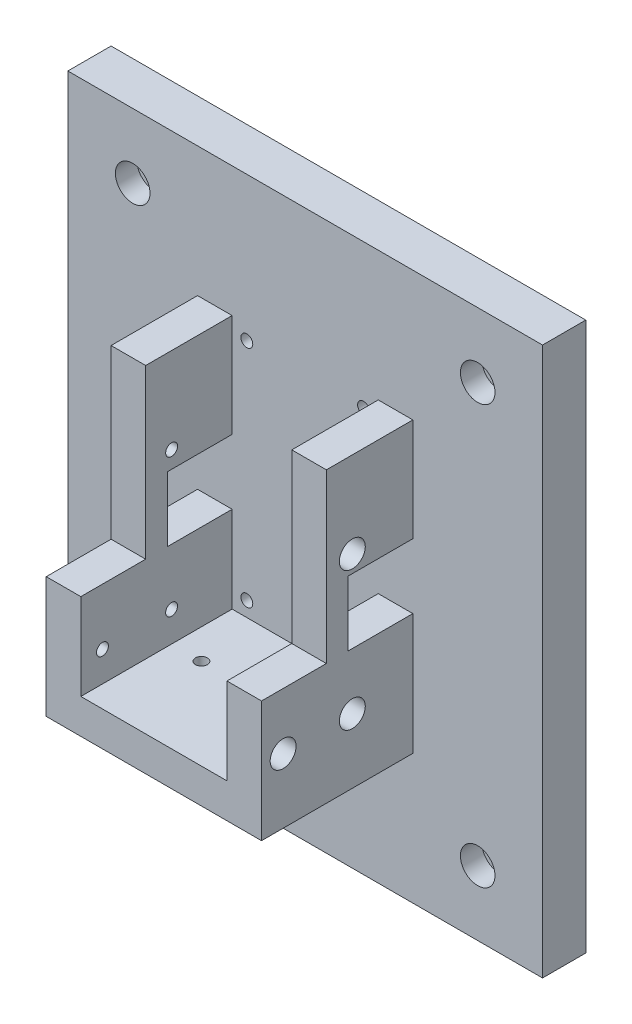
SolidWorks part; units mm, degrees
ref_plane "Front Plane" through (0, 0, 0) normal (0, 0, 1) x (1, 0, 0)
ref_plane "Top Plane" through (0, 0, 0) normal (0, 1, 0) x (1, 0, 0)
ref_plane "Right Plane" through (0, 0, 0) normal (1, 0, 0) x (0, 0, -1)
sketch "Sketch1" plane through (0, 0, 0) normal (0, 1, 0) x (1, 0, 0)
  line L1 (29.25, -16.75) -> (-29.25, -16.75)
  line L2 (29.25, -16.75) -> (29.25, 16.75)
  line L3 (29.25, 16.75) -> (-29.25, 16.75)
  line L4 (-29.25, -16.75) -> (-29.25, 16.75)
  line L5 (29.25, -16.75) -> (-29.25, 16.75) construction
  line L6 (29.25, 16.75) -> (-29.25, -16.75) construction
  line L7 (29.4, -16.9) -> (-29.4, -16.9)
  line L8 (29.4, -16.9) -> (29.4, 16.9)
  line L9 (29.4, 16.9) -> (-29.4, 16.9)
  line L10 (-29.4, -16.9) -> (-29.4, 16.9)
  line L11 (29.4, -16.9) -> (-29.4, 16.9) construction
  line L12 (29.4, 16.9) -> (-29.4, -16.9) construction
  line L13 (-29.4, 16.9) -> (29.4, 16.9)
  line L14 (-29.4, 16.9) -> (-29.4, 24.9)
  line L15 (-29.4, 24.9) -> (29.4, 24.9)
  line L16 (29.4, 16.9) -> (29.4, 24.9)
  line L17 (-29.4, -16.9) -> (29.4, -16.9)
  line L18 (-29.4, -16.9) -> (-29.4, -24.9)
  line L19 (-29.4, -24.9) -> (29.4, -24.9)
  line L20 (29.4, -16.9) -> (29.4, -24.9)
  point P0 (0, 0)
  point P6 (0, 0)
  dimension "D1" = 33.5
  dimension "D2" = 58.5
  dimension "D3" = 0.15
  dimension "D4" = 0.15
  dimension "D5" = 0
  dimension "D6" = 0
  dimension "D7" = 8
  dimension "D8" = 8
extrude "Boss-Extrude1" add sketch "Sketch1" along normal blind 25 contours L9 L16 L15 L14 | L20 L7 L18 L19 region at (0, 0, 20.9) region at (0, 0, -20.9)
extrude "Boss-Extrude2" add sketch "Sketch1<3>" along normal blind 5 contours L10 L7 L8 L9 L1 L4 L3 L2 | L4 L1 L2 L3 region at (0, 0, 0) region at (0, 0, 16.8322)
sketch "Sketch1<3>" plane through (0, 0, 0) normal (0, 1, 0) x (1, 0, 0) same geometry as "Sketch1"
sketch "Sketch2" plane through (0, 0, 0) normal (0, -1, 0) x (1, 0, 0)
  line L0 (-29.4, 24.9) -> (29.4, 24.9) construction
  line L2 (-29.4, 24.9) -> (-29.4, -24.9) construction
  circle A0 centre (-26.05, 13.5) radius 1.375
  circle A1 centre (-26.05, -13.5) radius 1.375
  circle A2 centre (25.95, -13.5) radius 1.375
  circle A3 centre (25.95, 13.5) radius 1.375
  dimension "D1" = 52
  dimension "D2" = 27
  dimension "D3" = 27
  dimension "D4" = 52
  dimension "D5" = 0
  dimension "D6" = 11.4
  dimension "D7" = 3.35
  dimension "D8" = 0
  dimension "D9" = 2.75
  dimension "D10" = 2.75
  dimension "D11" = 2.75
  dimension "D12" = 2.75
extrude "Cut-Extrude1" cut sketch "Sketch2" against normal blind 5
sketch "Sketch3" plane through (0, 0, 16.9) normal (0, 0, -1) x (-1, 0, 0)
  line L0 (-29.4, 5) -> (29.4, 5) construction
  line L1 (-29.4, 25) -> (-29.4, 5) construction
  circle A0 centre (-22.45, 19) radius 1.375
  circle A1 centre (9.55, 19) radius 1.375
  dimension "D1" = 14
  dimension "D2" = 32
  dimension "D3" = 2.75
  dimension "D4" = 14
  dimension "D5" = 2.75
  dimension "D6" = 6.95
extrude "Cut-Extrude2" cut sketch "Sketch3" against normal blind 20 and the other way blind 74
sketch "Sketch4" plane through (0, 0, -24.9) normal (0, 0, -1) x (-1, 0, 0)
  line L0 (-29.4, 25) -> (-29.4, 0) construction
  line L1 (-9.4, 5) -> (5.6, 5)
  line L2 (-9.4, 5) -> (-9.4, 20)
  line L3 (-9.4, 20) -> (5.6, 20)
  line L4 (5.6, 5) -> (5.6, 20)
  line L5 (-29.4, 5) -> (29.4, 5) construction
  dimension "D1" = 20
  dimension "D2" = 0
  dimension "D3" = 15
  dimension "D4" = 15
extrude "Cut-Extrude3" cut sketch "Sketch4" against normal blind 75
sketch "Sketch5" plane through (29.4, 0, 0) normal (1, 0, 0) x (0, 0, -1)
  line L1 (-24.9, 25) -> (24.9, 25)
  line L2 (-24.9, 25) -> (-24.9, 0)
  line L3 (-24.9, 0) -> (24.9, 0)
  line L4 (24.9, 25) -> (24.9, 0)
extrude "Boss-Extrude3" add sketch "Sketch5" along normal blind 8
sketch "Sketch6" plane through (37.4, 0, 0) normal (1, 0, 0) x (0, 0, -1)
  line L0 (-16.9, 5) -> (16.9, 5) construction
  line L1 (-24.9, 0) -> (24.9, 0) construction
  circle A0 centre (-10, 19) radius 1.375
  circle A1 centre (10, 19) radius 1.375
  point P8 (0, 0)
  dimension "D1" = 20
  dimension "D2" = 14
  dimension "D3" = 10
  dimension "D4" = 2.75
  dimension "D5" = 2.75
extrude "Cut-Extrude4" cut sketch "Sketch6" against normal blind 16
sketch "Sketch7" plane through (0, 0, 0) normal (0, -1, 0) x (1, 0, 0)
  line L1 (-29.4, 24.9) -> (37.4, 24.9)
  line L2 (-29.4, 24.9) -> (-29.4, -24.9)
  line L3 (-29.4, -24.9) -> (37.4, -24.9)
  line L4 (37.4, 24.9) -> (37.4, -24.9)
  circle A0 centre (-26.05, 13.5) radius 1.375
  circle A1 centre (25.95, 13.5) radius 1.375
  circle A2 centre (25.95, -13.5) radius 1.375
  circle A3 centre (-26.05, -13.5) radius 1.375
extrude "Boss-Extrude4" add sketch "Sketch7" along normal blind 5
sketch "Sketch8" plane through (0, -5, 0) normal (0, -1, 0) x (1, 0, 0)
  line L1 (-29.4, 24.9) -> (37.4, 24.9)
  line L2 (-29.4, 24.9) -> (-29.4, -24.9)
  line L3 (-29.4, -24.9) -> (37.4, -24.9)
  line L4 (37.4, 24.9) -> (37.4, -24.9)
  line L5 (-59.4, 54.9) -> (67.4, 54.9)
  line L6 (-59.4, 54.9) -> (-59.4, -54.9)
  line L7 (-59.4, -54.9) -> (67.4, -54.9)
  line L8 (67.4, 54.9) -> (67.4, -54.9)
  dimension "D1" = 30
  dimension "D2" = 30
  dimension "D3" = 30
  dimension "D4" = 30
extrude "Boss-Extrude5" add sketch "Sketch8" against normal blind 10
sketch "Sketch9" plane through (0, 25, 0) normal (0, 1, 0) x (1, 0, 0)
  line L1 (37.4, 24.9) -> (9.4, 24.9)
  line L2 (37.4, 24.9) -> (37.4, -24.9)
  line L3 (37.4, -24.9) -> (9.4, -24.9)
  line L4 (9.4, 24.9) -> (9.4, -24.9)
  line L5 (29.4, 16.9) -> (9.4, 16.9)
  line L6 (29.4, 16.9) -> (29.4, -16.9)
  line L7 (29.4, -16.9) -> (9.4, -16.9)
  line L8 (9.4, 16.9) -> (9.4, -16.9)
  line M1 (-29.4, 16.9) -> (29.4, 16.9)
  line M2 (29.4, 16.9) -> (29.4, -16.9)
  line M3 (29.4, -16.9) -> (-29.4, -16.9)
  line M5 (-29.4, -24.9) -> (37.4, -24.9)
  line M6 (37.4, -24.9) -> (37.4, 24.9)
  line M7 (37.4, 24.9) -> (-29.4, 24.9)
extrude "Boss-Extrude6" add sketch "Sketch9" along normal blind 15 contours L4 M7 M1 M2 M3 M5 M6 region at (36.8287, 25, 0)
sketch "Sketch11" plane through (0, 0, 24.9) normal (0, 0, 1) x (1, 0, 0)
  line L0 (9.4, 40) -> (9.4, 25) construction
  circle A0 centre (22.45, 35) radius 1.375
  circle A1 centre (22.45, 19) radius 1.375 construction
  dimension "D1" = 16
  dimension "D2" = 2.75
  dimension "D3" = 13.05
extrude "Cut-Extrude5" cut sketch "Sketch11" against normal blind 55
sketch "Sketch12" plane through (0, 5, 0) normal (0, 1, 0) x (1, 0, 0)
  line L0 (-59.4, -54.9) -> (-59.4, 54.9) construction
  line L1 (67.4, -54.9) -> (-59.4, -54.9) construction
  line L2 (-59.4, 54.9) -> (67.4, 54.9) construction
  line L3 (67.4, 54.9) -> (67.4, -54.9) construction
  circle A0 centre (-44.4, 39.9) radius 1.625
  circle A1 centre (52.4, 39.9) radius 1.625
  circle A2 centre (52.4, -39.9) radius 1.625
  circle A3 centre (-44.4, -39.9) radius 1.625
  dimension "D1" = 15
  dimension "D2" = 15
  dimension "D3" = 15
  dimension "D4" = 15
  dimension "D5" = 15
  dimension "D6" = 15
  dimension "D7" = 15
  dimension "D8" = 15
  dimension "D9" = 3.25
  dimension "D10" = 3.25
  dimension "D11" = 3.25
  dimension "D12" = 3.25
extrude "Cut-Extrude6" cut sketch "Sketch12" against normal blind 55
sketch "Sketch13" plane through (0, 0, 24.9) normal (0, 0, 1) x (1, 0, 0)
  circle A0 centre (-9.55, 19) radius 3
  circle A1 centre (22.45, 35) radius 3
  circle A2 centre (22.45, 19) radius 3
  dimension "D1" = 6
  dimension "D2" = 6
  dimension "D3" = 6
extrude "Cut-Extrude7" cut sketch "Sketch13" against normal blind 5
sketch "Sketch14" plane through (0, 0, -24.9) normal (0, 0, -1) x (-1, 0, 0)
  circle A0 centre (-22.45, 35) radius 3
  circle A1 centre (-22.45, 19) radius 3
  circle A2 centre (9.55, 19) radius 3
  dimension "D1" = 6
  dimension "D2" = 6
  dimension "D3" = 6
extrude "Cut-Extrude8" cut sketch "Sketch14" against normal blind 5
sketch "Sketch15" plane through (0, -5, 0) normal (0, -1, 0) x (1, 0, 0)
  circle A0 centre (-26.05, 13.5) radius 3
  circle A1 centre (25.95, 13.5) radius 3
  circle A2 centre (25.95, -13.5) radius 3
  circle A3 centre (-26.05, -13.5) radius 3
  dimension "D1" = 6
  dimension "D2" = 6
  dimension "D3" = 6
  dimension "D4" = 6
extrude "Cut-Extrude9" cut sketch "Sketch15" against normal blind 7
sketch "Sketch16" plane through (0, 5, 0) normal (0, 1, 0) x (1, 0, 0)
  circle A0 centre (-44.4, 39.9) radius 4
  circle A1 centre (52.4, 39.9) radius 4
  circle A2 centre (52.4, -39.9) radius 4
  circle A3 centre (-44.4, -39.9) radius 4
  dimension "D1" = 8
  dimension "D2" = 8
  dimension "D3" = 8
  dimension "D4" = 8
extrude "Cut-Extrude10" cut sketch "Sketch16" against normal blind 5
sketch "Sketch17" plane through (37.4, 0, 0) normal (1, 0, 0) x (0, 0, -1)
  circle A0 centre (-10, 19) radius 3
  circle A1 centre (10, 19) radius 3
  dimension "D1" = 6
  dimension "D2" = 6
extrude "Cut-Extrude11" cut sketch "Sketch17" against normal blind 5
move or copy body "Body-Move/Copy1" bodies to move or copy 118 copy no rotation origin (8.5, 13, -4.5) rotation axis (0.5774, -0.5774, -0.5774) rotation angle 120
